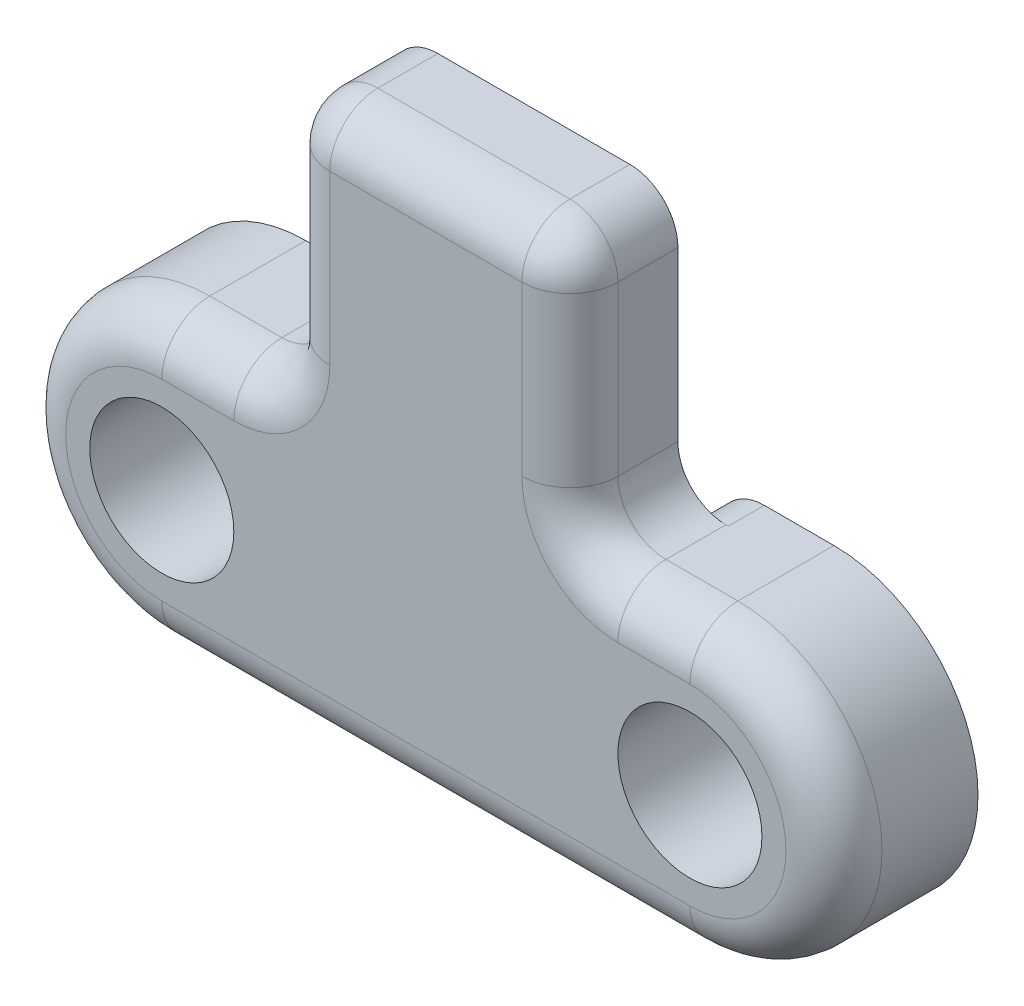
SolidWorks part; units mm, degrees
ref_plane "Front Plane" through (0, 0, 0) normal (0, 0, 1) x (1, 0, 0)
ref_plane "Top Plane" through (0, 0, 0) normal (0, 1, 0) x (1, 0, 0)
ref_plane "Right Plane" through (0, 0, 0) normal (1, 0, 0) x (0, 0, -1)
sketch "Sketch1" plane through (0, 0, 0) normal (0, 0, 1) x (1, 0, 0)
  line L0 (-5.5, 0) -> (5.5, 0)
  line L1 (-5.5, 0) -> (5.5, 0) construction
  line L2 (-5.5, 3) -> (5.5, 3)
  line L3 (-5.5, -3) -> (5.5, -3)
  line L5 (-3, 3) -> (3, 3)
  line L6 (-3, 3) -> (-3, 8.5)
  line L7 (-3, 8.5) -> (3, 8.5)
  line L8 (3, 3) -> (3, 8.5)
  circle A0 centre (5.5, 0) radius 1.5
  circle A1 centre (-5.5, 0) radius 1.5
  arc A2 (-5.5, 3) -> (-5.5, -3) centre (-5.5, 0) ccw
  arc A3 (5.5, -3) -> (5.5, 3) centre (5.5, 0) ccw
  point P4 (0, 0)
  point P8 (0, 0)
  point P17 (0, 8.5)
  point P18 (0, 3)
  dimension "D1" = 3
  dimension "D3" = 3
  dimension "D2" = 11
  dimension "D4" = 5.5
  dimension "D5" = 6
extrude "Boss-Extrude1" add sketch "Sketch1" along normal blind 3 contours L3 A3 L2 A2 A1 A0 | L6 L5 L8 L7 region at (-4.25, 2.8197, 0)
sketch "Sketch2" plane through (0, 0, 0) normal (0, 1, 0) x (1, 0, 0)
  line L0 (-5.5, 0) -> (-3, 0) construction
  line L1 (-3.05, 0) -> (3.05, 0)
  line L2 (-3.05, 0) -> (-3.05, -0.75)
  line L3 (-3.05, -0.75) -> (3.05, -0.75)
  line L4 (3.05, 0) -> (3.05, -0.75)
  point P6 (0, -0.75)
  dimension "D1" = 6.1
  dimension "D2" = 0.75
extrude "Cut-Extrude1" cut sketch "Sketch2" against normal through all both and the other way through all
fillet "Fillet2" radius 1 4 edges at (3, 3, 1.875) (-3, 3, 1.875) (3, 8.5, 1.875) (-3, 8.5, 1.875)
fillet "Fillet1" radius 1 16 edges at (-8.5, 0, 3) (0, -3, 3) (8.5, 0, 3) (3.05, -3, 0.375) (-3.05, -3, 0.375) (-4.75, 3, 3) (4.75, 3, 3) (3.2929, 3.2929, 3) (3, 5.75, 3) (2.7071, 8.2071, 3) (0, 8.5, 3) (-2.7071, 8.2071, 3) (-3, 5.75, 3) (-3.2929, 3.2929, 3) (-3.05, 3.6878, 0.375) (3.05, 3.6878, 0.375)
